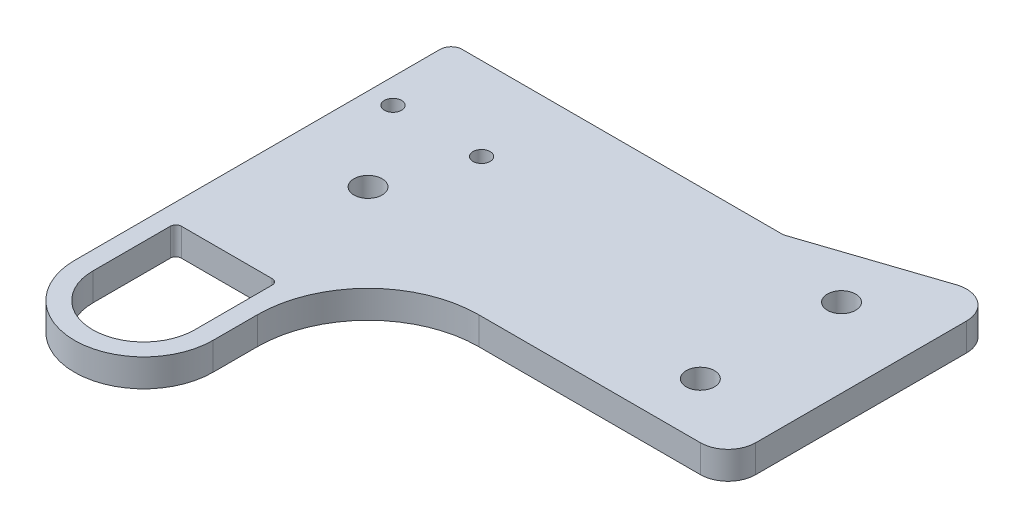
SolidWorks part; units mm, degrees
ref_plane "正面" through (0, 0, 0) normal (0, 0, 1) x (1, 0, 0)
ref_plane "平面" through (0, 0, 0) normal (0, 1, 0) x (1, 0, 0)
ref_plane "右側面" through (0, 0, 0) normal (1, 0, 0) x (0, 0, -1)
sketch "ｽｹｯﾁ1" plane through (0, 0, 0) normal (0, 1, 0) x (1, 0, 0)
  line L0 (0, 0) -> (180, 0) construction
  line L1 (180, 0) -> (180, 60) construction
  line L2 (0, 0) -> (0, -48)
  line L3 (0, -48) -> (25, -48) construction
  line L4 (25, -48) -> (25, -20)
  line L5 (180, 60) -> (0, 0) construction
  line L6 (0, 0) -> (90, 30)
  line L7 (90, 30) -> (90, -20)
  line L8 (90, -20) -> (25, -20)
  line L9 (0, -10) -> (90, -10) construction
  line L10 (90, 19.4591) -> (0, -10.5409) construction
  arc A0 (0, -48) -> (25, -48) centre (12.5, -48) ccw
  circle A1 centre (75.7698, 14.7157) radius 2.55
  circle A2 centre (75, -10) radius 2.55
  circle A3 centre (15, -10) radius 2.55
  circle A4 centre (12.5, -48) radius 7.5
  dimension "D5" = 25
  dimension "D9" = 15
  dimension "D12" = 5.1
  dimension "D13" = 15
  dimension "D1" = 60
  dimension "D2" = 180
  dimension "D3" = 20
  dimension "D4" = 90
  dimension "D6" = 28
  dimension "D7" = 10
  dimension "D8" = 10
  dimension "D10" = 15
  dimension "D11" = 15
extrude "ﾎﾞｽ - 押し出し1" add sketch "ｽｹｯﾁ1" along normal blind 5
fillet "ﾌｨﾚｯﾄ1" radius 20 1 edges at (25, 2.5, 20)
fillet "ﾌｨﾚｯﾄ2" radius 5 2 edges at (90, 2.5, -30) (90, 2.5, 20)
sketch "ｽｹｯﾁ2" plane through (0, 5, 0) normal (0, 1, 0) x (1, 0, 0)
  line L0 (3.3, -48) -> (3.3, -34)
  line L1 (4.3, -33) -> (20.7, -33)
  line L2 (21.7, -34) -> (21.7, -48)
  arc A0 (3.3, -48) -> (21.7, -48) centre (12.5, -48) ccw
  arc A1 (3.3, -34) -> (4.3, -33) centre (4.3, -34) cw
  arc A2 (20.7, -33) -> (21.7, -34) centre (20.7, -34) cw
  point P10 (21.7, -33)
  dimension "D1" = 9.2
  dimension "D3" = 1
  dimension "D2" = 15
extrude "ｶｯﾄ - 押し出し1" cut sketch "ｽｹｯﾁ2" against normal through all
sketch "ｽｹｯﾁ4" plane through (0, 5, 0) normal (0, 1, 0) x (1, 0, 0)
  line L0 (0, 0) -> (0, 20)
  line L1 (0, 20) -> (60, 20)
  line L2 (83.4189, 27.8063) -> (0, 0) construction
  line L3 (60, 20) -> (0, 0)
  dimension "D1" = 20
extrude "ﾎﾞｽ - 押し出し2" add sketch "ｽｹｯﾁ4" against normal up to surface (5 mm away) up to face at (12.5, 0, 39.7976)
sketch "ｽｹｯﾁ3" plane through (0, 5, 0) normal (0, 1, 0) x (1, 0, 0)
  line L0 (12.5, -60.5) -> (12.5, 5) construction
  line L1 (12.5, 5) -> (20.5, 5) construction
  line L2 (20.7, -33) -> (4.3, -33) construction
  arc A0 (0, -48) -> (25, -48) centre (12.5, -48) ccw construction
  circle A1 centre (20.5, 5) radius 1.55
  circle A2 centre (4.5, 5) radius 1.55
  dimension "D1" = 3.1
  dimension "D2" = 38
  dimension "D3" = 8
extrude "ｶｯﾄ - 押し出し2" cut sketch "ｽｹｯﾁ3" against normal through all
fillet "ﾌｨﾚｯﾄ3" radius 2 2 edges at (60, 2.5, -20) (0, 2.5, -20)
